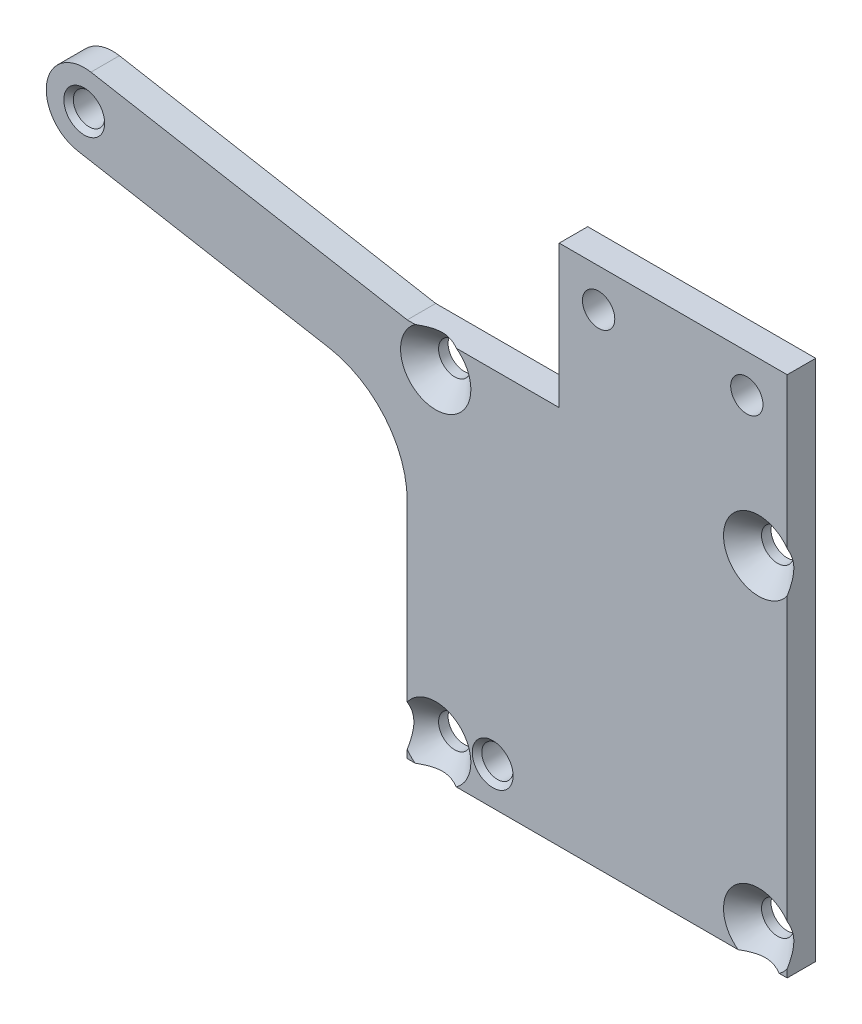
SolidWorks part; units mm, degrees
ref_plane "Front Plane" through (0, 0, 0) normal (0, 0, 1) x (1, 0, 0)
ref_plane "Top Plane" through (0, 0, 0) normal (0, 1, 0) x (1, 0, 0)
ref_plane "Right Plane" through (0, 0, 0) normal (1, 0, 0) x (0, 0, -1)
sketch "Sketch1" plane through (0, 0, 0) normal (0, 0, 1) x (1, 0, 0)
  line L2 (20, 20) -> (20, -20)
  line L3 (20, -20) -> (-20, -20)
  line L4 (-20, 3.4993) -> (-20, -20)
  line L5 (20, 20) -> (-20, -20) construction
  line L6 (20, -20) -> (-20, 20) construction
  line L7 (17, 17) -> (-17, 17) construction
  line L8 (17, 17) -> (17, -17) construction
  line L9 (17, -17) -> (-17, -17) construction
  line L10 (-17, 17) -> (-17, -17) construction
  line L11 (17, 17) -> (-17, -17) construction
  line L12 (17, -17) -> (-17, 17) construction
  line L13 (20, 35) -> (-4, 35)
  line L14 (-4, 35) -> (-4, 20)
  line L15 (-4, 20) -> (-20, 20)
  line L16 (-4, 31) -> (19.9, 31) construction
  line L17 (-53.2978, 25.9379) -> (-20, 20)
  line L18 (-54.7022, 18.0621) -> (-28.2444, 13.344)
  line L19 (-20, 3.4993) -> (-20, 20) construction
  line L20 (20, 20) -> (20, 35)
  line L21 (-4, 20) -> (20, 20) construction
  circle A0 centre (-17, 17) radius 1.7
  circle A1 centre (17, 17) radius 1.7
  circle A2 centre (17, -17) radius 1.7
  circle A3 centre (-17, -17) radius 1.7
  circle A4 centre (0.15, 31) radius 1.7
  circle A5 centre (15.75, 31) radius 1.7
  circle A6 centre (-11, -16) radius 1.65
  circle A7 centre (-54, 22) radius 1.65
  arc A8 (-53.2978, 25.9379) -> (-54.7022, 18.0621) centre (-54, 22) ccw
  arc A9 (-20, 3.4993) -> (-28.2444, 13.344) centre (-30, 3.4993) ccw
  point P0 (0, 0)
  point P5 (0, 0)
  point P25 (7.95, 31)
  point P28 (-54, 22)
  dimension "D4" = 3.4
  dimension "D5" = 3.4
  dimension "D6" = 3.4
  dimension "D7" = 3.4
  dimension "D12" = 7.8
  dimension "D14" = 3.4
  dimension "D15" = 3.4
  dimension "D16" = 9
  dimension "D17" = 4
  dimension "D18" = 3.3
  dimension "D21" = 3.3
  dimension "D22" = 8
  dimension "D23" = 10
  dimension "D9" = 4.15
  dimension "D2" = 40
  dimension "D3" = 34
  dimension "D8" = 15
  dimension "D10" = 24
  dimension "D11" = 4
  dimension "D13" = 7.8
  dimension "D19" = 34
  dimension "D20" = 2
  dimension "D24" = 34
  dimension "D25" = 3
extrude "Boss-Extrude1" add sketch "Sketch1" along normal blind 3
chamfer "Chamfer1" distance 2 angle 45 4 edges at (18.7, 17, 3) (18.7, -17, 3) (-15.3, -17, 3) (-15.3, 17, 3)
chamfer "Chamfer2" distance 0.5 angle 45 2 edges at (-9.35, -16, 3) (-52.35, 22, 3)
